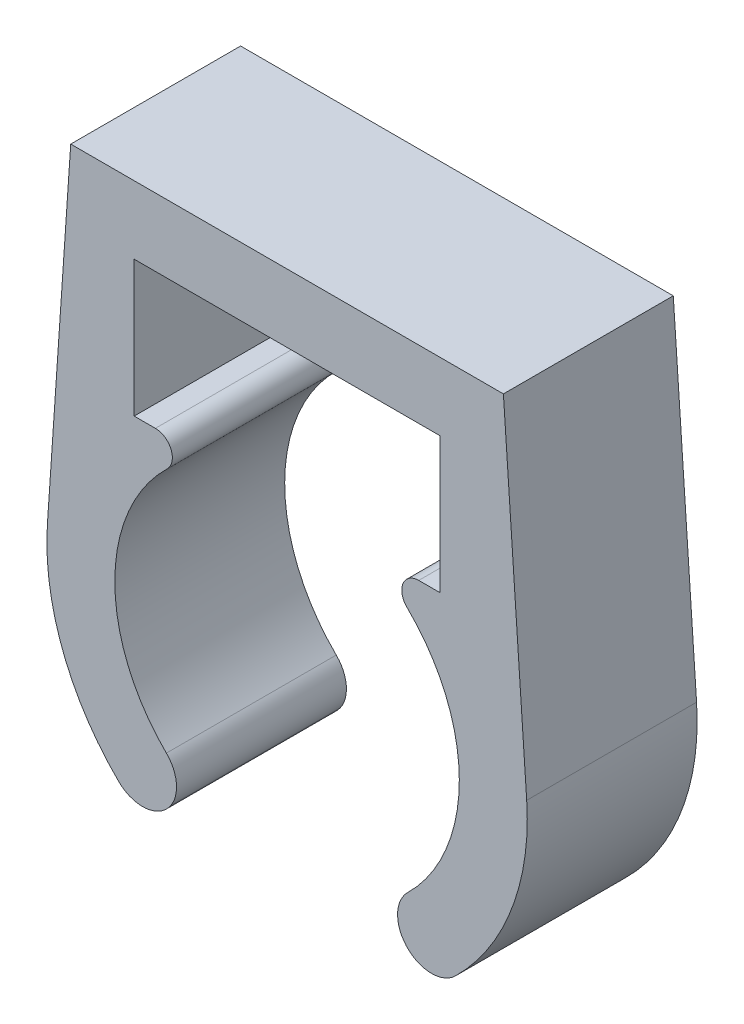
SolidWorks part; units mm, degrees
ref_plane "Front Plane" through (0, 0, 0) normal (0, 0, 1) x (1, 0, 0)
ref_plane "Top Plane" through (0, 0, 0) normal (0, 1, 0) x (1, 0, 0)
ref_plane "Right Plane" through (0, 0, 0) normal (1, 0, 0) x (0, 0, -1)
sketch "Sketch1" plane through (0, 0, 0) normal (0, 0, 1) x (1, 0, 0)
  line L0 (-7.0535, 0.4828) -> (-6.3678, 10.5)
  line L1 (4.5, 8.5) -> (-4.5, 8.5)
  line L2 (4.5, 8.5) -> (4.5, 4.5)
  line L3 (4.5, 4.5) -> (-4.5, 4.5)
  line L4 (-4.5, 8.5) -> (-4.5, 4.5)
  line L5 (4.5, 8.5) -> (-4.5, 4.5) construction
  line L6 (4.5, 4.5) -> (-4.5, 8.5) construction
  line L7 (-6.3678, 10.5) -> (6.3678, 10.5)
  line L8 (6.3678, 10.5) -> (7.0535, 0.4828)
  line L9 (0, 0) -> (0, 50000) construction
  line L10 (0, 0) -> (8.0129, -11.4437)
  line L11 (0, 0) -> (-8.0129, -11.4437)
  circle A0 centre (0, 0) radius 5
  circle A1 centre (0, 0) radius 5.07
  arc A2 (-7.0535, 0.4828) -> (7.0535, 0.4828) centre (0, 0) ccw
  point P5 (0, 6.5)
  dimension "D1" = 10
  dimension "D2" = 0.07
  dimension "2" = 2
  dimension "D4" = 9
  dimension "D5" = 4
  dimension "D6" = 6.5
  dimension "D7" = 14.107
  dimension "D8" = 12.7355
  dimension "D9" = 2
  dimension "D10" = 2
  dimension "35" = 35
extrude "Boss-Extrude1" add sketch "Sketch1" along normal blind 5 contours L0 A2 L8 L7 L4 L1 L2 L3 A1 region at (-6.4954, 5.4767, 0)
fillet "Fillet1" radius 1 4 edges at (4.0552, -5.7914, 2.5) (2.908, -4.1531, 2.5) (-4.0552, -5.7914, 2.5) (-2.908, -4.1531, 2.5)
fillet "Fillet3" radius 0.5 2 edges at (2.3356, 4.5, 2.5) (-2.3356, 4.5, 2.5)
